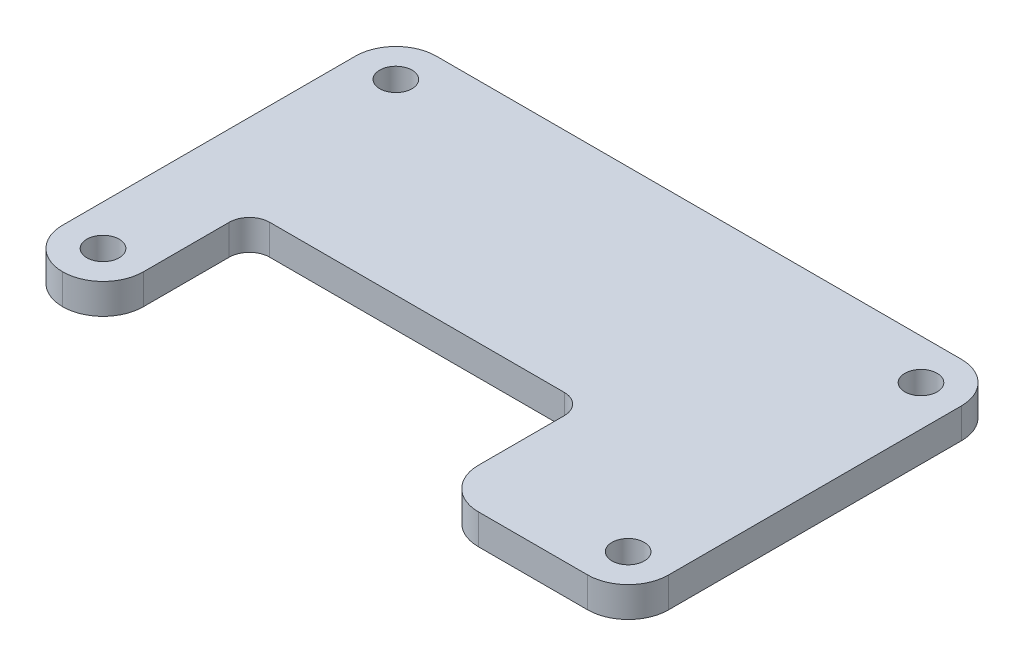
SolidWorks part; units mm, degrees
ref_plane "Front Plane" through (0, 0, 0) normal (0, 0, 1) x (1, 0, 0)
ref_plane "Top Plane" through (0, 0, 0) normal (0, 1, 0) x (1, 0, 0)
ref_plane "Right Plane" through (0, 0, 0) normal (1, 0, 0) x (0, 0, -1)
sketch "Sketch1" plane through (0, 0, 0) normal (0, 1, 0) x (1, 0, 0)
  line L1 (-30, -18.5) -> (30, -18.5)
  line L2 (-30, -18.5) -> (-30, 18.5)
  line L3 (-30, 18.5) -> (30, 18.5)
  line L4 (30, -18.5) -> (30, 18.5)
  line L5 (-30, -18.5) -> (30, 18.5) construction
  line L6 (-30, 18.5) -> (30, -18.5) construction
  point P0 (0, 0)
  dimension "D1" = 37
  dimension "D2" = 60
extrude "Boss-Extrude1" add sketch "Sketch1" along normal blind 2.9972
fillet "Fillet1" radius 4 4 edges at (-30, 1.4986, -18.5) (30, 1.4986, -18.5) (30, 1.4986, 18.5) (-30, 1.4986, 18.5)
sketch "Sketch2" plane through (0, 2.9972, 0) normal (0, 1, 0) x (1, 0, 0)
  circle A0 centre (-26, 14.5) radius 1.6
  circle A1 centre (-26, -14.5) radius 1.6
  circle A2 centre (26, -14.5) radius 1.6
  circle A3 centre (26, 14.5) radius 1.6
  dimension "D1" = 3.2
extrude "Cut-Extrude1" cut sketch "Sketch2" against normal through all
sketch "Sketch3" plane through (0, 2.9972, 0) normal (0, 1, 0) x (1, 0, 0)
  line L1 (-22, -4) -> (11.176, -4)
  line L2 (-22, -4) -> (-22, -18.5)
  line L3 (-22, -18.5) -> (11.176, -18.5)
  line L4 (11.176, -4) -> (11.176, -18.5)
  line L5 (-22, -4) -> (11.176, -18.5) construction
  line L6 (-22, -18.5) -> (11.176, -4) construction
  line L7 (-26, -18.5) -> (26, -18.5) construction
  circle A0 centre (-26, -14.5) radius 1.6 construction
  point P0 (-5.412, -11.25)
  dimension "D3" = 4
  dimension "D1" = 11.176
  dimension "D2" = 4
extrude "Cut-Extrude2" cut sketch "Sketch3" against normal through all
fillet "Fillet2" radius 4 2 edges at (-22, 1.4986, 18.5) (11.176, 1.4986, 18.5)
fillet "Fillet3" radius 2 2 edges at (11.176, 1.4986, 4) (-22, 1.4986, 4)
